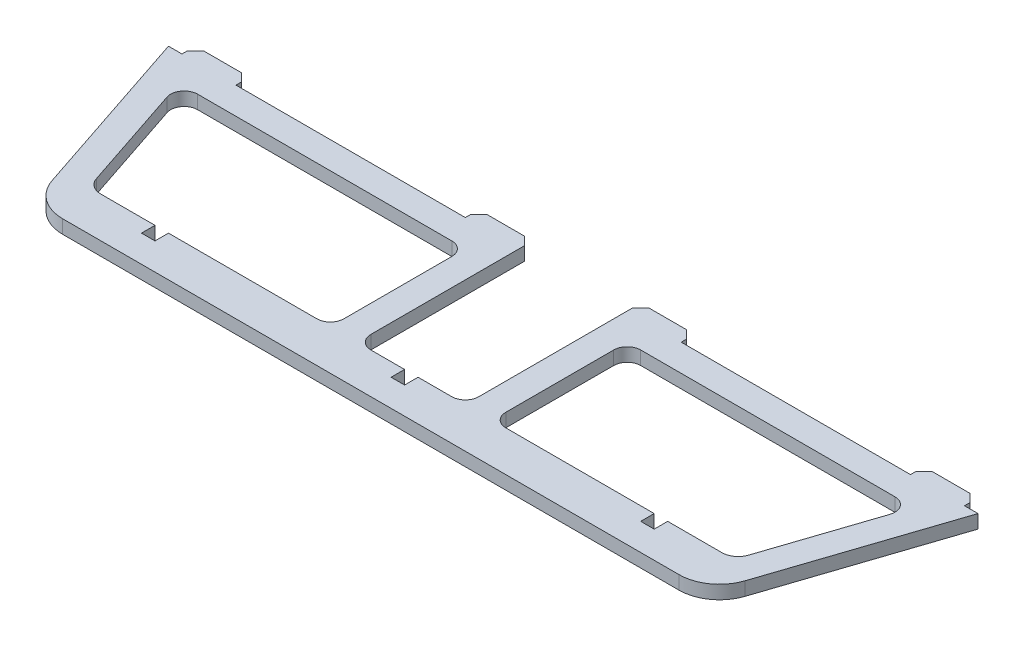
SolidWorks part; units mm, degrees
material "Stal węglowa"
ref_plane "Front" through (0, 0, 0) normal (0, 0, 1) x (1, 0, 0)
ref_plane "Top" through (0, 0, 0) normal (0, 1, 0) x (1, 0, 0)
ref_plane "Right" through (0, 0, 0) normal (1, 0, 0) x (0, 0, -1)
sketch "Szkic2" plane through (0, 0, 0) normal (0, 1, 0) x (1, 0, 0)
  line L161 (-233.2033, -150.4583) -> (-461.5805, -150.4583)
  line L162 (-344.8919, -140.4583) -> (-349.8919, -140.4583)
  line L163 (-344.8919, -135.4583) -> (-344.8919, -140.4583)
  line L164 (-312.3919, -85.4583) -> (-218.2033, -85.4583)
  line L165 (-327.3919, -73.4583) -> (-327.3919, -130.4583)
  line L166 (-317.3919, -90.4583) -> (-317.3919, -130.4583)
  line L167 (-344.8919, -135.4583) -> (-332.3919, -135.4583)
  line L168 (-197.3919, -75.4583) -> (-218.9731, -140.2017)
  line L169 (-213.4599, -92.0394) -> (-226.5653, -131.3557)
  line L170 (-252.3919, -140.4583) -> (-257.3919, -140.4583)
  line L171 (-252.3919, -135.4583) -> (-252.3919, -140.4583)
  line L172 (-252.3919, -135.4583) -> (-232.2574, -135.4583)
  line L173 (-257.3919, -135.4583) -> (-312.3919, -135.4583)
  line L174 (-257.3919, -135.4583) -> (-257.3919, -140.4583)
  line L175 (-367.3919, -73.4583) -> (-367.3919, -130.4583)
  line L176 (-442.3919, -140.4583) -> (-437.3919, -140.4583)
  line L177 (-387.3919, -75.4583) -> (-387.3919, -73.4583)
  line L178 (-497.3919, -75.4583) -> (-475.8108, -140.2017)
  line L179 (-481.324, -92.0394) -> (-468.2186, -131.3557)
  line L180 (-437.3919, -135.4583) -> (-437.3919, -140.4583)
  line L181 (-442.3919, -135.4583) -> (-462.5265, -135.4583)
  line L182 (-492.3919, -75.4583) -> (-492.3919, -73.4583)
  line L183 (-442.3919, -135.4583) -> (-442.3919, -140.4583)
  line L184 (-489.3919, -70.4583) -> (-475.3919, -70.4583)
  line L185 (-437.3919, -135.4583) -> (-382.3919, -135.4583)
  line L186 (-387.3919, -75.4583) -> (-472.3919, -75.4583)
  line L187 (-472.3919, -73.4583) -> (-472.3919, -75.4583)
  line L188 (-384.3919, -70.4583) -> (-370.3919, -70.4583)
  line L189 (-382.3919, -85.4583) -> (-476.5805, -85.4583)
  line L190 (-349.8919, -135.4583) -> (-349.8919, -140.4583)
  line L191 (-349.8919, -135.4583) -> (-362.3919, -135.4583)
  line L192 (-377.3919, -90.4583) -> (-377.3919, -130.4583)
  line L193 (-492.3919, -75.4583) -> (-497.3919, -75.4583)
  line L194 (-219.3919, -70.4583) -> (-222.3919, -73.4583)
  line L195 (-202.3919, -73.4583) -> (-205.3919, -70.4583)
  line L196 (-324.3919, -70.4583) -> (-327.3919, -73.4583)
  line L197 (-202.3919, -75.4583) -> (-202.3919, -73.4583)
  line L198 (-307.3919, -75.4583) -> (-307.3919, -73.4583)
  line L199 (-222.3919, -73.4583) -> (-222.3919, -75.4583)
  line L200 (-307.3919, -73.4583) -> (-310.3919, -70.4583)
  line L201 (-310.3919, -70.4583) -> (-324.3919, -70.4583)
  line L202 (-202.3919, -75.4583) -> (-197.3919, -75.4583)
  line L203 (-205.3919, -70.4583) -> (-219.3919, -70.4583)
  line L204 (-307.3919, -75.4583) -> (-222.3919, -75.4583)
  line L205 (-370.3919, -70.4583) -> (-367.3919, -73.4583)
  line L206 (-387.3919, -73.4583) -> (-384.3919, -70.4583)
  line L207 (-492.3919, -73.4583) -> (-489.3919, -70.4583)
  line L208 (-475.3919, -70.4583) -> (-472.3919, -73.4583)
  arc A74 (-312.3919, -85.4583) -> (-317.3919, -90.4583) centre (-312.3919, -90.4583) ccw
  arc A75 (-213.4599, -92.0394) -> (-218.2033, -85.4583) centre (-218.2033, -90.4583) ccw
  arc A76 (-332.3919, -135.4583) -> (-327.3919, -130.4583) centre (-332.3919, -130.4583) ccw
  arc A77 (-317.3919, -130.4583) -> (-312.3919, -135.4583) centre (-312.3919, -130.4583) ccw
  arc A78 (-233.2033, -150.4583) -> (-218.9731, -140.2017) centre (-233.2033, -135.4583) ccw
  arc A79 (-232.2574, -135.4583) -> (-226.5653, -131.3557) centre (-232.2574, -129.4583) ccw
  arc A80 (-367.3919, -130.4583) -> (-362.3919, -135.4583) centre (-362.3919, -130.4583) ccw
  arc A81 (-475.8108, -140.2017) -> (-461.5805, -150.4583) centre (-461.5805, -135.4583) ccw
  arc A82 (-382.3919, -135.4583) -> (-377.3919, -130.4583) centre (-382.3919, -130.4583) ccw
  arc A83 (-476.5805, -85.4583) -> (-481.324, -92.0394) centre (-476.5805, -90.4583) ccw
  arc A84 (-377.3919, -90.4583) -> (-382.3919, -85.4583) centre (-382.3919, -90.4583) ccw
  arc A85 (-468.2186, -131.3557) -> (-462.5265, -135.4583) centre (-462.5265, -129.4583) ccw
extrude "Dodanie-wyciągnięcie1" add sketch "Szkic2" along normal blind 5
